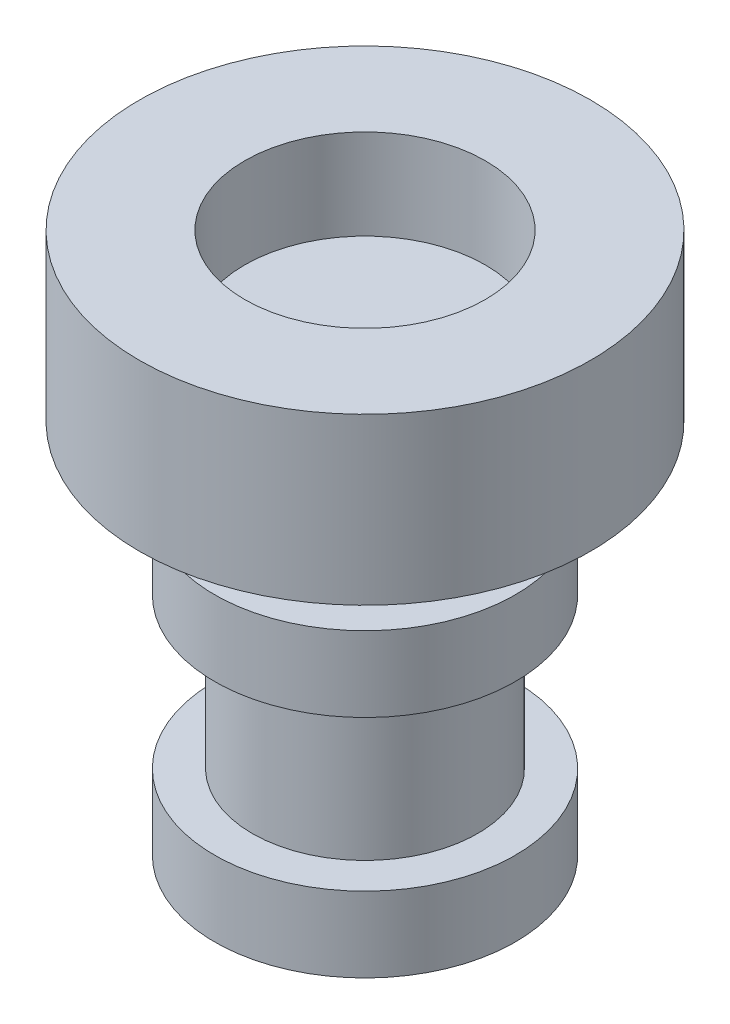
SolidWorks part; units mm, degrees
ref_plane "Front Plane" through (0, 0, 0) normal (0, 0, 1) x (1, 0, 0)
ref_plane "Top Plane" through (0, 0, 0) normal (0, 1, 0) x (1, 0, 0)
ref_plane "Right Plane" through (0, 0, 0) normal (1, 0, 0) x (0, 0, -1)
sketch "Sketch1" plane through (0, 0, 0) normal (0, 1, 0) x (1, 0, 0)
  circle A0 centre (-0.522, 0.5111) radius 1.6
  circle A1 centre (-0.522, 0.5111) radius 3
  dimension "D1" = 3.2
  dimension "D2" = 6
extrude "Boss-Extrude1" add sketch "Sketch1" along normal blind 2.2
extrude "Boss-Extrude2" add sketch "Sketch1<3>" along normal blind 1 contours A0 region at (-0.522, 0, -0.5111)
sketch "Sketch1<3>" plane through (0, 0, 0) normal (0, 1, 0) x (1, 0, 0) same geometry as "Sketch1"
sketch "Sketch5" plane through (0, 0, 0) normal (0, -1, 0) x (1, 0, 0)
  circle A2 centre (-0.522, -0.5111) radius 1.5
  circle A3 centre (-0.522, -0.5111) radius 1.5
  dimension "D2" = 3
  dimension "D1" = 1.5
extrude "Boss-Extrude3" add sketch "Sketch5" along normal blind 1 contours A3
sketch "Sketch6" plane through (0, -1, 0) normal (0, -1, 0) x (1, 0, 0)
  circle A0 centre (-0.522, -0.5111) radius 2
  dimension "D1" = 4
extrude "Boss-Extrude4" add sketch "Sketch6" along normal blind 1
sketch "Sketch8" plane through (0, -2, 0) normal (0, -1, 0) x (-1, 0, 0)
  circle A0 centre (0.522, 0.5111) radius 1.5
  dimension "D1" = 3
extrude "Boss-Extrude5" add sketch "Sketch8" along normal blind 3 contours A0
sketch "Sketch10" plane through (0, -5, 0) normal (0, -1, 0) x (1, 0, 0)
  circle A0 centre (-0.522, -0.5111) radius 2
extrude "Boss-Extrude6" add sketch "Sketch10" against normal blind 1
